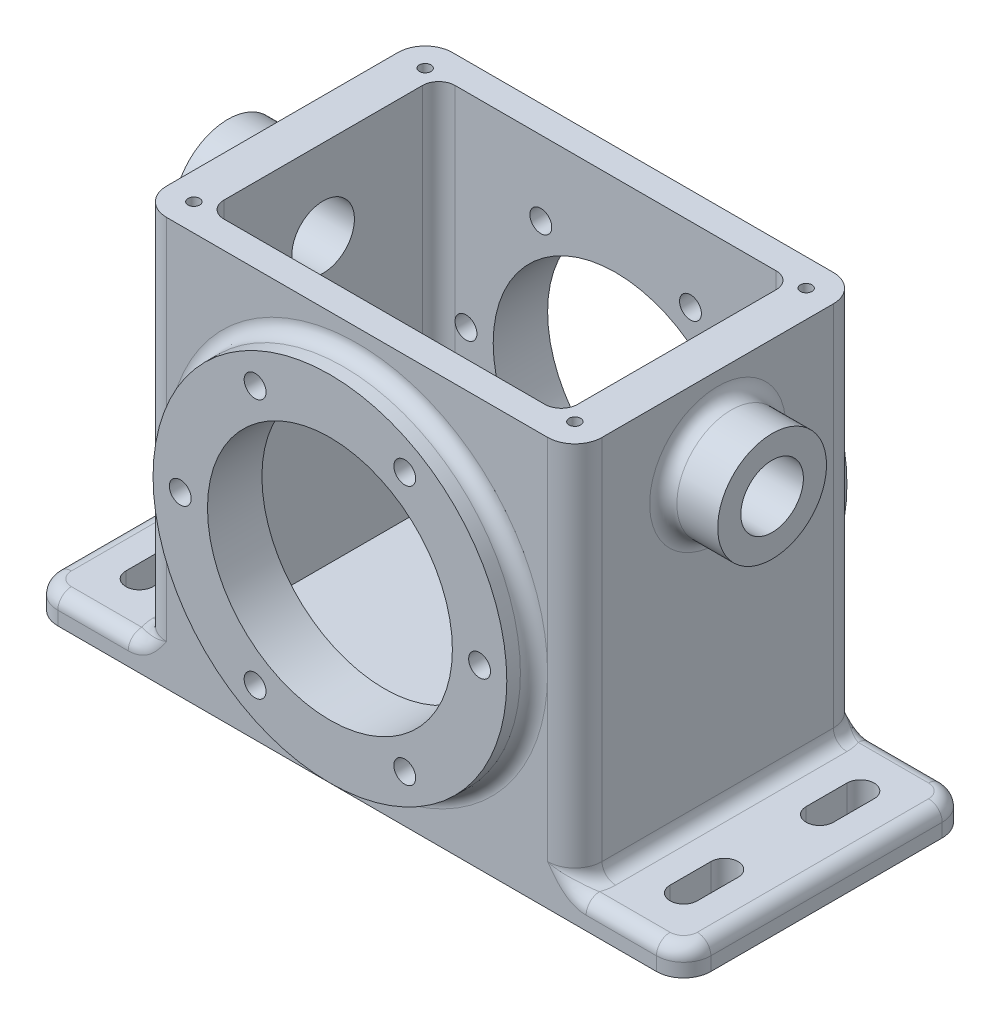
SolidWorks part; units mm, degrees
material "Cast Alloy Steel"
ref_plane "Front Plane" through (0, 0, 0) normal (0, 0, 1) x (1, 0, 0)
ref_plane "Top Plane" through (0, 0, 0) normal (0, 1, 0) x (1, 0, 0)
ref_plane "Right Plane" through (0, 0, 0) normal (1, 0, 0) x (0, 0, -1)
sketch "Sketch2" plane through (0, 0, 0) normal (0, 1, 0) x (1, 0, 0)
  line L0 (-1270.7662, 0) -> (1270.7662, 0) construction
  line L1 (-76.2, -33.3375) -> (76.2, -33.3375)
  line L2 (-76.2, -33.3375) -> (-76.2, 33.3375)
  line L3 (-76.2, 33.3375) -> (76.2, 33.3375)
  line L4 (76.2, -33.3375) -> (76.2, 33.3375)
  line L5 (-76.2, -33.3375) -> (76.2, 33.3375) construction
  line L6 (-76.2, 33.3375) -> (76.2, -33.3375) construction
  point P0 (0, 0)
  dimension "D1" = 152.4
  dimension "D2" = 66.675
extrude "Boss-Extrude1" add sketch "Sketch2" along normal blind 6.35
sketch "Sketch3" plane through (0, 6.35, 0) normal (0, 1, 0) x (1, 0, 0)
  line L0 (-76.2, -33.3375) -> (76.2, -33.3375) construction
  line L1 (-50.8, 33.3375) -> (50.8, 33.3375)
  line L2 (-50.8, 33.3375) -> (-50.8, -33.3375)
  line L3 (-50.8, -33.3375) -> (50.8, -33.3375)
  line L4 (50.8, 33.3375) -> (50.8, -33.3375)
  line L5 (-50.8, 33.3375) -> (50.8, -33.3375) construction
  line L6 (-50.8, -33.3375) -> (50.8, 33.3375) construction
  point P0 (0, 0)
  dimension "D1" = 101.6
extrude "Boss-Extrude2" add sketch "Sketch3" along normal blind 88.9 contours L2 L1 L4 L3
fillet "Fillet1" radius 6.35 8 edges at (76.2, 3.175, -33.3375) (76.2, 3.175, 33.3375) (-76.2, 3.175, 33.3375) (-76.2, 3.175, -33.3375) (-50.8, 50.8, -33.3375) (-50.8, 50.8, 33.3375) (50.8, 50.8, 33.3375) (50.8, 50.8, -33.3375)
fillet "Fillet2" radius 3.175 16 edges at (-74.3401, 6.35, -31.4776) (-57.15, 6.35, -33.3375) (-48.9401, 6.35, -31.4776) (-50.8, 6.35, 0) (-48.9401, 6.35, 31.4776) (-57.15, 6.35, 33.3375) (-74.3401, 6.35, 31.4776) (-76.2, 6.35, 0) (74.3401, 6.35, 31.4776) (57.15, 6.35, 33.3375) (48.9401, 6.35, 31.4776) (50.8, 6.35, 0) (48.9401, 6.35, -31.4776) (57.15, 6.35, -33.3375) (74.3401, 6.35, -31.4776) (76.2, 6.35, 0)
sketch "Sketch4" plane through (0, 95.25, 0) normal (0, 1, 0) x (1, 0, 0)
  line L0 (-44.45, 33.3375) -> (44.45, 33.3375) construction
  line L1 (37.465, -26.9875) -> (-37.465, -26.9875)
  line L2 (41.275, -23.1775) -> (41.275, 23.1775)
  line L3 (37.465, 26.9875) -> (-37.465, 26.9875)
  line L4 (-41.275, -23.1775) -> (-41.275, 23.1775)
  line L5 (41.275, -26.9875) -> (-41.275, 26.9875) construction
  line L6 (41.275, 26.9875) -> (-41.275, -26.9875) construction
  line L7 (-50.8, 26.9875) -> (-50.8, -26.9875) construction
  arc A0 (-37.465, -26.9875) -> (-41.275, -23.1775) centre (-37.465, -23.1775) cw
  arc A1 (37.465, -26.9875) -> (41.275, -23.1775) centre (37.465, -23.1775) ccw
  arc A2 (41.275, 23.1775) -> (37.465, 26.9875) centre (37.465, 23.1775) ccw
  arc A3 (-37.465, 26.9875) -> (-41.275, 23.1775) centre (-37.465, 23.1775) ccw
  point P0 (0, 0)
  dimension "D3" = 3.81
  dimension "D1" = 6.35
  dimension "D2" = 9.525
extrude "Top Cut" cut sketch "Sketch4" against normal blind 85.725
sketch "Sketch7" plane through (0, 0, 33.3375) normal (0, 0, 1) x (1, 0, 0)
  line L0 (-44.45, 95.25) -> (44.45, 95.25) construction
  circle A0 centre (0, 47.625) radius 41.275
  dimension "D1" = 47.625
  dimension "D2" = 82.55
sketch "Sketch8" plane through (50.8, 0, 0) normal (1, 0, 0) x (0, 0, -1)
  line L0 (26.9875, 95.25) -> (-26.9875, 95.25) construction
  circle A0 centre (0, 76.2) radius 12.7
  dimension "D1" = 25.4
  dimension "D2" = 19.05
extrude "Boss-Extrude4" add sketch "Sketch8" along normal blind 12.7 contours A0
mirror "Mirror3" about plane through (0, 0, 0) normal (1, 0, 0) of "Boss-Extrude4" second plane through (0, 0, 0) second plane normal (0, 0, 1)
sketch "Sketch12" plane through (0, 0, 33.3375) normal (0, 0, 1) x (1, 0, 0)
  line L0 (-44.45, 95.25) -> (44.45, 95.25) construction
  circle A0 centre (0, 47.625) radius 41.275
  dimension "D1" = 82.55
  dimension "D2" = 47.625
extrude "Boss-Extrude5" add sketch "Sketch12" along normal blind 6.35 contours A0
sketch "Sketch13" plane through (0, 0, 39.6875) normal (0, 0, 1) x (1, 0, 0)
  line L0 (-44.45, 95.25) -> (44.45, 95.25) construction
  circle A0 centre (0, 47.625) radius 28.575
  dimension "D1" = 57.15
  dimension "D2" = 47.625
mirror "Mirror7" about plane through (0, 0, 0) normal (0, 0, 1) of "Boss-Extrude5"
extrude "Cut-Extrude2" cut sketch "Sketch13" against normal through all contours A0
sketch "Sketch14" plane through (63.5, 0, 0) normal (1, 0, 0) x (0, 0, -1)
  circle A0 centre (0, 76.2) radius 7.3025
  circle A2 centre (0, 76.2) radius 12.7 construction
  dimension "D1" = 14.605
extrude "Cut-Extrude3" cut sketch "Sketch14" against normal through all contours A0
hole_wizard "1/4-20 Tapped Hole1" positions "Sketch16" profile "Sketch17" tap size "1/4-20" standard "ANSI Inch"
sketch "Sketch16" plane through (0, 0, 39.6875) normal (0, 0, 1) x (1, 0, 0)
  line L0 (28.575, 47.625) -> (41.275, 47.625) construction
  circle A0 centre (0, 47.625) radius 28.575 construction
  circle A1 centre (0, 47.625) radius 41.275 construction
  point P0 (34.925, 47.625)
  point P12 (34.925, 47.625)
sketch "Sketch17" plane through (34.925, 47.625, 39.6875) normal (1, 0, 0) x (0, -1, 0)
  line L0 (0, 0) -> (0, 12.7)
  line L1 (0, 12.7) -> (2.5527, 12.7)
  line L2 (2.5527, 12.7) -> (2.5527, 0)
  line L5 (2.5527, 0) -> (0, 0)
  line L11 (0, -6.35) -> (0, 107.95) construction
  dimension "Thru Tap Drill Dia." = 5.1054
  dimension "Thru Tap Drill Depth" = 12.7
cosmetic thread "Hole Thread1" parameters "D2"=6.35
pattern_circular "CirPattern1" count 6 over 360 about axis through (0, 47.625, 0) along (0, 0, 1) of "1/4-20 Tapped Hole1"
cosmetic thread "Hole Thread2" parameters "D2"=6.35
cosmetic thread "Hole Thread3" parameters "D2"=6.35
cosmetic thread "Hole Thread4" parameters "D2"=6.35
cosmetic thread "Hole Thread5" parameters "D2"=6.35
cosmetic thread "Hole Thread6" parameters "D2"=6.35
mirror "Mirror8" about plane through (0, 0, 0) normal (0, 0, 1) of "CirPattern1", "1/4-20 Tapped Hole1"
cosmetic thread "Hole Thread7" parameters "D2"=6.35
cosmetic thread "Hole Thread8" parameters "D2"=6.35
cosmetic thread "Hole Thread9" parameters "D2"=6.35
cosmetic thread "Hole Thread10" parameters "D2"=6.35
cosmetic thread "Hole Thread11" parameters "D2"=6.35
cosmetic thread "Hole Thread12" parameters "D2"=6.35
hole_wizard "#6-32 Tapped Hole1" positions "Sketch20" profile "Sketch21" tap size "#6-32" standard "ANSI Inch"
sketch "Sketch20" plane through (0, 95.25, 0) normal (0, 1, 0) x (1, 0, 0)
  point P0 (44.45, 26.9875)
  point P3 (-44.45, 26.9875)
  point P6 (-44.45, -26.9875)
  point P9 (44.45, -26.9875)
sketch "Sketch21" plane through (44.45, 95.25, -26.9875) normal (1, 0, 0) x (0, 0, 1)
  line L0 (0, 0) -> (0, 11.7855)
  line L1 (0, 11.7855) -> (1.3525, 10.9728)
  line L2 (1.3525, 10.9728) -> (1.3525, 0)
  line L5 (1.3525, 0) -> (0, 0)
  line L10 (0, 11.7855) -> (-1.3525, 10.9728) construction
  line L11 (0, -6.35) -> (0, 107.95) construction
  dimension "Tap Drill Dia." = 2.7051
  dimension "Tap Drill Depth" = 10.9728
  dimension "Drill Angle" = 118
cosmetic thread "Hole Thread13" parameters "D1"=7.0104, "D2"=3.5052
cosmetic thread "Hole Thread14" parameters "D1"=7.0104, "D2"=3.5052
cosmetic thread "Hole Thread15" parameters "D1"=7.0104, "D2"=3.5052
cosmetic thread "Hole Thread16" parameters "D1"=7.0104, "D2"=3.5052
sketch "Sketch22" plane through (0, 6.35, 0) normal (0, 1, 0) x (1, 0, 0)
  line L0 (-63.5, -20.6375) -> (-63.5, -11.1125) construction
  line L1 (-53.4303, -33.3375) -> (-69.85, -33.3375) construction
  line L2 (-66.675, -20.6375) -> (-66.675, -11.1125)
  line L3 (-60.325, -20.6375) -> (-60.325, -11.1125)
  line L4 (-76.2, -26.9875) -> (-76.2, 26.9875) construction
  arc A0 (-66.675, -20.6375) -> (-60.325, -20.6375) centre (-63.5, -20.6375) ccw
  arc A1 (-60.325, -11.1125) -> (-66.675, -11.1125) centre (-63.5, -11.1125) ccw
  point P4 (-63.5, -15.875)
  dimension "D1" = 6.35
  dimension "D2" = 9.525
  dimension "D3" = 12.7
  dimension "D4" = 12.7
extrude "Cut-Extrude4" cut sketch "Sketch22" against normal through all contours L3 A1 L2 A0
pattern_linear "LPattern1" count 2 spacing 31.75 along (0, 0, -1) of "Cut-Extrude4"
mirror "Mirror9" about plane through (0, 0, 0) normal (1, 0, 0) of "LPattern1", "Cut-Extrude4"
fillet "Fillet3" radius 3.175 4 edges at (50.8, 76.2, -12.7) (-50.8, 76.2, -12.7) (-41.275, 47.625, 33.3375) (41.275, 47.625, -33.3375)
